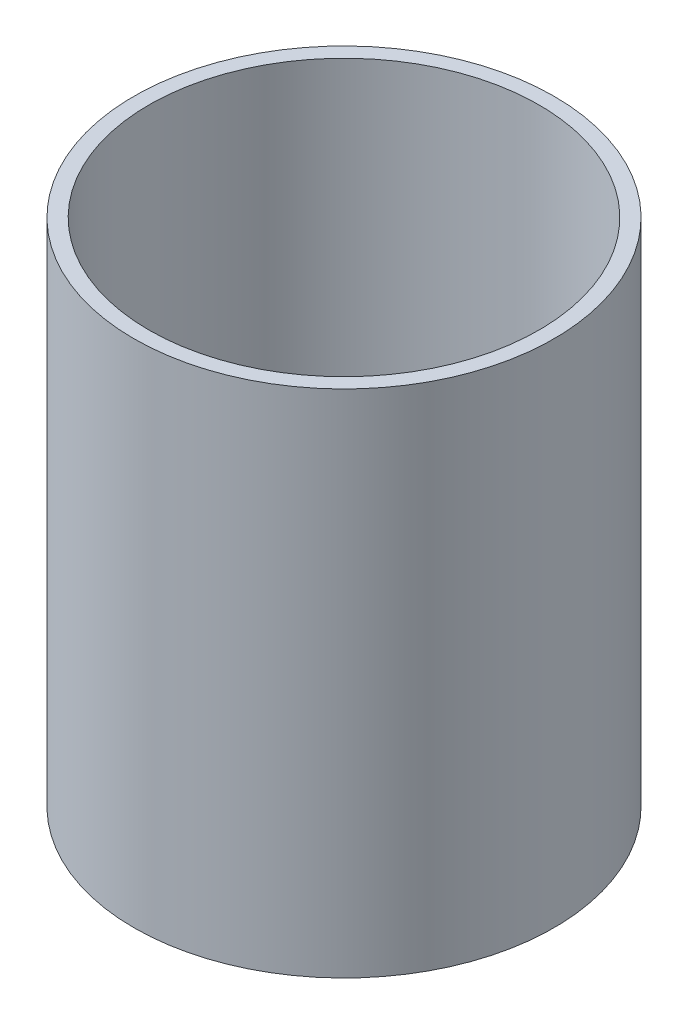
SolidWorks part; units mm, degrees
ref_plane "Front Plane" through (0, 0, 0) normal (0, 0, 1) x (1, 0, 0)
ref_plane "Top Plane" through (0, 0, 0) normal (0, 1, 0) x (1, 0, 0)
ref_plane "Right Plane" through (0, 0, 0) normal (1, 0, 0) x (0, 0, -1)
ref_axis "Axis1" through (0, 55, 0) along (0, -1, 0)
sketch "Sketch1" plane through (0, 0, 0) normal (0, 0, 1) x (1, 0, 0)
  line L1 (-44.45, 36.9791) -> (-41.275, 36.9791)
  line L2 (-44.45, 36.9791) -> (-44.45, -70.9709)
  line L3 (-44.45, -70.9709) -> (-41.275, -70.9709)
  line L4 (-41.275, 36.9791) -> (-41.275, -70.9709)
  line L5 (0, 36.9791) -> (-38.1, 36.9791) construction
  line L6 (0, -70.9709) -> (-38.1, -70.9709) construction
  point P4 (0, 0)
  point P6 (-44.45, 49.6791)
  point P8 (-41.275, -80.265)
  point P9 (-41.275, -82.6816)
revolve "Revolve1" add sketch "Sketch1" angle 360 about axis through (0, 55, 0) along (0, -1, 0)
